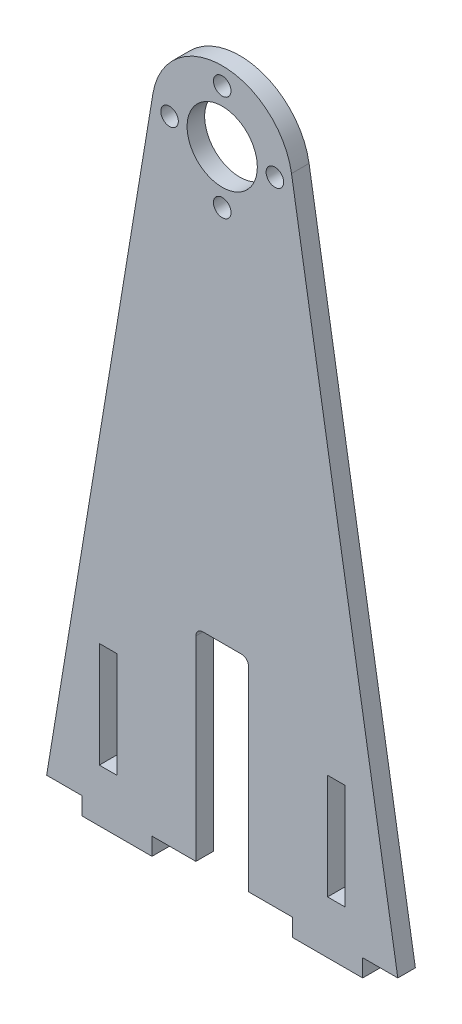
SolidWorks part; units mm, degrees
material "Pine"
ref_plane "Front Plane" through (0, 0, 0) normal (0, 0, 1) x (1, 0, 0)
ref_plane "Top Plane" through (0, 0, 0) normal (0, 1, 0) x (1, 0, 0)
ref_plane "Right Plane" through (0, 0, 0) normal (1, 0, 0) x (0, 0, -1)
sketch "Sketch1" plane through (0, 0, 0) normal (0, 0, 1) x (1, 0, 0)
  line L0 (0, 0) -> (0, 228.6) construction
  line L1 (25.4, 0) -> (9.525, 0)
  line L2 (-25.4, 0) -> (-25.4, -6.35)
  line L3 (-25.4, -6.35) -> (-50.8, -6.35)
  line L4 (-50.8, -6.35) -> (-50.8, 0)
  line L5 (-50.8, 0) -> (-63.5, 0)
  line L6 (-63.5, 0) -> (-25.0605, 232.739)
  line L7 (0, 228.6) -> (0, 159.1888) construction
  line L8 (50.8, 0) -> (63.5, 0)
  line L9 (50.8, -6.35) -> (50.8, 0)
  line L10 (25.4, 0) -> (25.4, -6.35)
  line L11 (25.4, -6.35) -> (50.8, -6.35)
  line L12 (63.5, 0) -> (25.0605, 232.739)
  line L13 (44.45, 12.7) -> (38.1, 12.7)
  line L14 (-44.45, 12.7) -> (-38.1, 12.7)
  line L15 (-44.45, 12.7) -> (-44.45, 50.8)
  line L16 (-44.45, 50.8) -> (-38.1, 50.8)
  line L17 (-38.1, 12.7) -> (-38.1, 50.8)
  line L22 (44.45, 12.7) -> (44.45, 50.8)
  line L23 (44.45, 50.8) -> (38.1, 50.8)
  line L24 (38.1, 12.7) -> (38.1, 50.8)
  line L25 (-9.525, 73.1663) -> (9.525, 73.1663)
  line L26 (9.525, 73.1663) -> (9.525, 0)
  line L27 (-38.1, 0) -> (-38.1, 12.7) construction
  line L28 (-44.45, 12.7) -> (-44.45, 0) construction
  line L30 (-9.525, 73.1663) -> (-9.525, 0)
  line L31 (-9.525, 0) -> (-25.4, 0)
  arc A0 (25.0605, 232.739) -> (-25.0605, 232.739) centre (0, 228.6) ccw
  circle A1 centre (0, 228.6) radius 12.7
  circle A3 centre (0, 247.65) radius 3.175
  circle A4 centre (19.05, 228.6) radius 3.175
  circle A5 centre (0, 209.55) radius 3.175
  circle A6 centre (-19.05, 228.6) radius 3.175
  point P11 (0, 0)
  point P42 (0, 228.6)
  point P43 (0, 73.1663)
  dimension "D5" = 12.7
  dimension "D7" = 25.4
  dimension "D8" = 19.05
  dimension "D13" = 6.35
  dimension "D1" = 63.5
  dimension "D2" = 6.35
  dimension "D3" = 25.4
  dimension "D4" = 25.4
  dimension "D6" = 228.6
  dimension "D10" = 38.1
  dimension "D11" = 12.7
  dimension "D12" = 19.05
  dimension "D14" = 4
extrude "Boss-Extrude1" add sketch "Sketch1" along normal blind 6.35
fillet "Fillet1" radius 2.54 1 edges at (-9.525, 73.1663, 3.175)
fillet "Fillet2" radius 2.54 1 edges at (9.525, 73.1663, 3.175)
